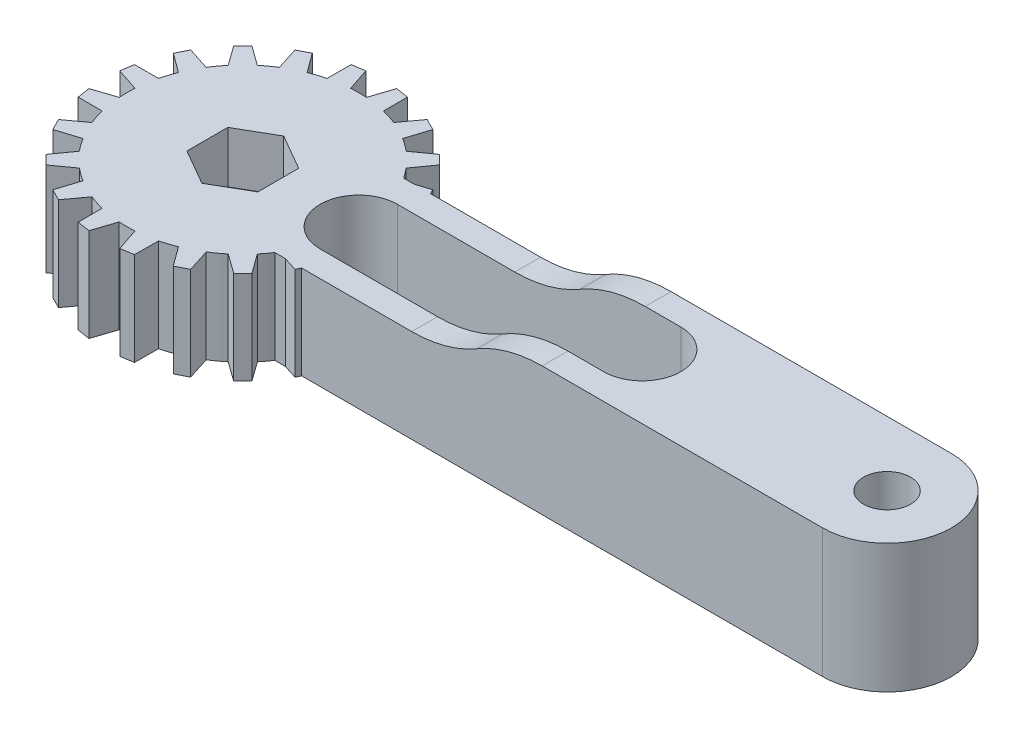
SolidWorks part; units mm, degrees
material "ABS"
ref_plane "Ebene vorne" through (0, 0, 0) normal (0, 0, 1) x (1, 0, 0)
ref_plane "Ebene oben" through (0, 0, 0) normal (0, 1, 0) x (1, 0, 0)
ref_plane "Ebene rechts" through (0, 0, 0) normal (1, 0, 0) x (0, 0, -1)
sketch "Skizze1" plane through (0, 0, 0) normal (0, 1, 0) x (1, 0, 0)
  line L0 (0, 0) -> (50, 0) construction
  line L1 (0, 5) -> (50, 5)
  line L2 (0, -5) -> (50, -5)
  arc A0 (0, 5) -> (0, -5) centre (0, 0) ccw
  arc A1 (50, -5) -> (50, 5) centre (50, 0) ccw
  circle A2 centre (50, 0) radius 1.825
  circle A3 centre (0, 0) radius 1.825
  point P3 (25, 0)
  dimension "D3" = 3.65
  dimension "D4" = 3.65
  dimension "D1" = 50
  dimension "D2" = 5
extrude "Aufsatz-Linear austragen1" add sketch "Skizze1" against normal blind 10
sketch "Skizze5" plane through (0, 0, 0) normal (0, 1, 0) x (1, 0, 0)
  line L0 (0, -5) -> (25, -5)
  line L1 (0, -5) -> (50, -5) construction
  line L2 (25, -5) -> (25, 5)
  line L3 (50, 5) -> (0, 5) construction
  line L4 (25, 5) -> (0, 5)
  arc A0 (0, 5) -> (0, -5) centre (0, 0) ccw
  arc A1 (0, 5) -> (0, -5) centre (0, 0) ccw construction
extrude "Schnitt-Linear austragen1" cut sketch "Skizze5" against normal blind 2.75
fillet "Verrundung1" radius 10 1 edges at (25, -2.75, 0)
fillet "Verrundung2" radius 10 1 edges at (25, 0, 0)
sketch "Skizze2" plane through (0, -2.75, 0) normal (0, 1, 0) x (1, 0, 0)
  circle A0 centre (0, 0) radius 5
  circle A1 centre (0, 0) radius 9
  arc A3 (0, 5) -> (0, -5) centre (0, 0) ccw construction
  dimension "D1" = 18
extrude "Aufsatz-Linear austragen2" add sketch "Skizze2" against normal up to surface (7.25 mm away) up to face at (0, -10, 1.825)
sketch "Skizze3" plane through (0, -2.75, 0) normal (0, 1, 0) x (1, 0, 0)
  line L0 (-12.8224, 0) -> (0, 0) construction
  line L1 (0, 0) -> (-12.8224, 2.0309) construction
  line L2 (-8.9792, 0.6122) -> (-10.7453, 1.1956)
  line L3 (-10.7453, 1.1956) -> (-10.5888, 2.1833)
  line L4 (-8.7289, 2.1925) -> (-10.5888, 2.1833)
  circle A0 centre (0, 0) radius 9 construction
  arc A1 (-8.9792, 0.6122) -> (-8.7289, 2.1925) centre (0, 0) cw
  point P5 (-8.8892, 1.4079)
  point P12 (-10.667, 1.6895)
  dimension "D1" = 9
  dimension "D2" = 0.5
  dimension "D3" = 0.8
  dimension "D4" = 1.8
extrude "Aufsatz-Linear austragen3" add sketch "Skizze3" against normal up to surface (7.25 mm away) up to face at (25.8708, -10, 0)
pattern_circular "Kreismuster1" count 20 over 360 about axis through (0, -2.75, 0) along (0, 1, 0) of "Aufsatz-Linear austragen3"
sketch "Skizze6" plane through (0, 0, 0) normal (0, 1, 0) x (1, 0, 0)
  line L1 (50, 3.1754) -> (47.25, 1.5877)
  line L2 (47.25, 1.5877) -> (47.25, -1.5877)
  line L3 (47.25, -1.5877) -> (50, -3.1754)
  line L4 (50, -3.1754) -> (52.75, -1.5877)
  line L5 (52.75, -1.5877) -> (52.75, 1.5877)
  line L6 (52.75, 1.5877) -> (50, 3.1754)
  circle A0 centre (50, 0) radius 2.75 construction
  dimension "D1" = 5.5
extrude "Schnitt-Linear austragen2" [suppressed] cut sketch "Skizze6" against normal blind 5
sketch "Skizze8" plane through (0, -2.75, 0) normal (0, 1, 0) x (1, 0, 0)
  line L1 (0, 3.1754) -> (-2.75, 1.5877)
  line L2 (-2.75, 1.5877) -> (-2.75, -1.5877)
  line L3 (-2.75, -1.5877) -> (0, -3.1754)
  line L4 (0, -3.1754) -> (2.75, -1.5877)
  line L5 (2.75, -1.5877) -> (2.75, 1.5877)
  line L6 (2.75, 1.5877) -> (0, 3.1754)
  circle A0 centre (0, 0) radius 2.75 construction
  dimension "D1" = 5.5
extrude "Schnitt-Linear austragen3" cut sketch "Skizze8" against normal blind 4
sketch "Skizze10" plane through (0, -10, 0) normal (0, -1, 0) x (1, 0, 0)
  line L0 (9, 0) -> (31, 0) construction
  line L1 (9, 3) -> (31, 3)
  line L2 (9, -3) -> (31, -3)
  arc A0 (9, 3) -> (9, -3) centre (9, 0) ccw
  arc A1 (31, -3) -> (31, 3) centre (31, 0) ccw
  point P3 (20, 0)
  dimension "D1" = 6
  dimension "D2" = 22
  dimension "D3" = 20
extrude "Schnitt-Linear austragen4" cut sketch "Skizze10" against normal through all
